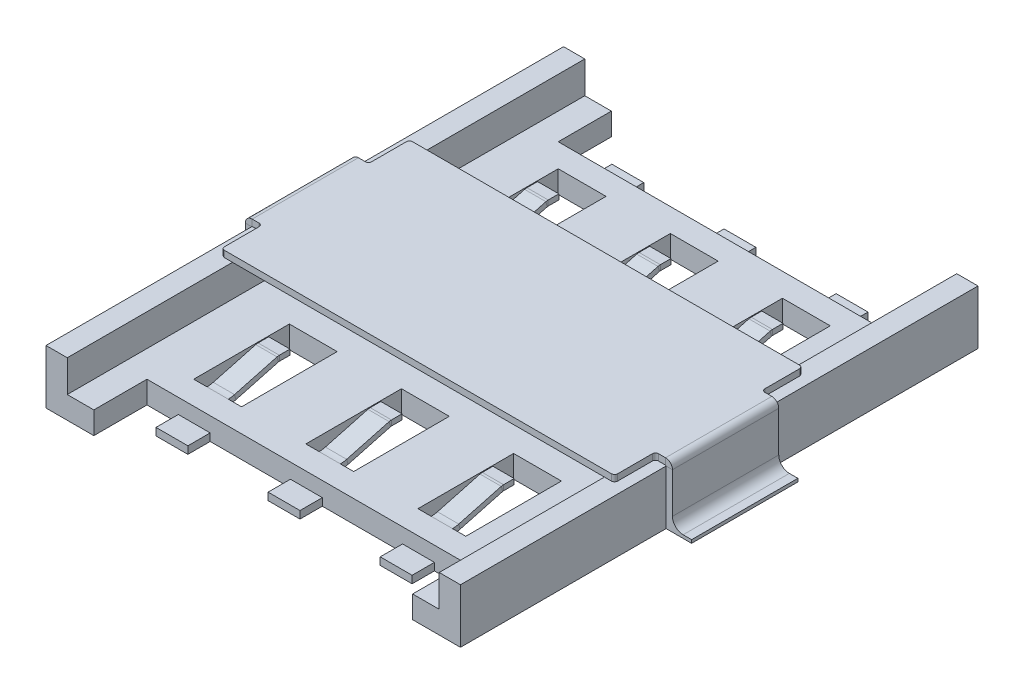
SolidWorks part; units mm, degrees
ref_plane "Front Plane" through (0, 0, 0) normal (0, 0, 1) x (1, 0, 0)
ref_plane "Top Plane" through (0, 0, 0) normal (0, 1, 0) x (1, 0, 0)
ref_plane "Right Plane" through (0, 0, 0) normal (1, 0, 0) x (0, 0, -1)
sketch "Sketch1" plane through (0, 0, 0) normal (0, 1, 0) x (1, 0, 0)
  line L1 (-4.953, 6.1849) -> (4.953, 6.1849)
  line L2 (-4.953, 6.1849) -> (-4.953, -6.1849)
  line L3 (-4.953, -6.1849) -> (4.953, -6.1849)
  line L4 (4.953, 6.1849) -> (4.953, -6.1849)
  point P4 (0, -6.1849)
  point P6 (-4.953, 0)
  dimension "D1" = 9.906
  dimension "D2" = 12.3698
extrude "Boss-Extrude1" add sketch "Sketch1" along normal blind 0.5334
sketch "Sketch2" plane through (0, 0.5334, 0) normal (0, 1, 0) x (1, 0, 0)
  line L0 (-4.953, -6.1849) -> (4.953, -6.1849) construction
  line L1 (-4.953, 6.1849) -> (-4.445, 6.1849)
  line L2 (-4.953, 6.1849) -> (-4.953, -6.1849)
  line L3 (-4.953, -6.1849) -> (-4.445, -6.1849)
  line L4 (-4.445, 6.1849) -> (-4.445, -6.1849)
  line L6 (4.445, -6.1849) -> (4.953, -6.1849)
  line L7 (4.445, -6.1849) -> (4.445, 6.1849)
  line L8 (4.445, 6.1849) -> (4.953, 6.1849)
  line L9 (4.953, -6.1849) -> (4.953, 6.1849)
  dimension "D1" = 0.508
extrude "Boss-Extrude2" add sketch "Sketch2" along normal blind 0.762
sketch "Sketch3" plane through (0, 0.5334, 0) normal (0, 1, 0) x (1, 0, 0)
  line L0 (4.445, 6.1849) -> (-4.445, 6.1849) construction
  line L1 (-3.81, 6.1849) -> (3.81, 6.1849)
  line L2 (-3.81, 6.1849) -> (-3.81, 4.9149)
  line L3 (-3.81, 4.9149) -> (3.81, 4.9149)
  line L4 (3.81, 6.1849) -> (3.81, 4.9149)
  line L5 (-4.445, -6.1849) -> (4.445, -6.1849) construction
  line L6 (-3.81, -6.1849) -> (3.81, -6.1849)
  line L7 (-3.81, -6.1849) -> (-3.81, -4.9149)
  line L8 (-3.81, -4.9149) -> (3.81, -4.9149)
  line L9 (3.81, -6.1849) -> (3.81, -4.9149)
  line L10 (-4.953, 6.1849) -> (-4.953, -6.1849) construction
  point P14 (0, 4.9149)
  point P15 (0, 6.1849)
  point P16 (0, -4.9149)
  dimension "D1" = 1.143
  dimension "D2" = 1.27
extrude "Cut-Extrude1" cut sketch "Sketch3" against normal up to next
sketch "Sketch4" plane through (0, 0.5334, 0) normal (0, 1, 0) x (1, 0, 0)
  line L0 (-3.81, 4.9149) -> (3.81, 4.9149) construction
  line L1 (-3.2512, 4.3561) -> (-2.1082, 4.3561)
  line L2 (-3.2512, 4.3561) -> (-3.2512, 2.0701)
  line L3 (-3.2512, 2.0701) -> (-2.1082, 2.0701)
  line L4 (-2.1082, 4.3561) -> (-2.1082, 2.0701)
  line L5 (-4.953, 6.1849) -> (-4.953, -6.1849) construction
  line L6 (-2.1082, 2.0701) -> (-0.5715, 2.0701) construction
  line L7 (-0.5715, 4.3561) -> (0.5715, 4.3561)
  line L8 (-0.5715, 4.3561) -> (-0.5715, 2.0701)
  line L9 (-0.5715, 2.0701) -> (0.5715, 2.0701)
  line L10 (0.5715, 4.3561) -> (0.5715, 2.0701)
  line L11 (2.1082, 4.3561) -> (3.2512, 4.3561)
  line L12 (2.1082, 4.3561) -> (2.1082, 2.0701)
  line L13 (2.1082, 2.0701) -> (3.2512, 2.0701)
  line L14 (3.2512, 4.3561) -> (3.2512, 2.0701)
  line L15 (0.5715, 2.0701) -> (2.1082, 2.0701) construction
  line L16 (-4.445, 0) -> (4.445, 0) construction
  line L17 (-4.445, -6.1849) -> (-4.445, 6.1849) construction
  line L18 (4.445, 6.1849) -> (4.445, -6.1849) construction
  line L19 (0.5715, -2.0701) -> (2.1082, -2.0701) construction
  line L20 (-2.1082, -2.0701) -> (-0.5715, -2.0701) construction
  line L21 (3.2512, -4.3561) -> (3.2512, -2.0701)
  line L22 (2.1082, -2.0701) -> (3.2512, -2.0701)
  line L23 (2.1082, -4.3561) -> (2.1082, -2.0701)
  line L24 (2.1082, -4.3561) -> (3.2512, -4.3561)
  line L25 (0.5715, -4.3561) -> (0.5715, -2.0701)
  line L26 (-0.5715, -2.0701) -> (0.5715, -2.0701)
  line L27 (-0.5715, -4.3561) -> (-0.5715, -2.0701)
  line L28 (-0.5715, -4.3561) -> (0.5715, -4.3561)
  line L29 (-2.1082, -4.3561) -> (-2.1082, -2.0701)
  line L30 (-3.2512, -2.0701) -> (-2.1082, -2.0701)
  line L31 (-3.2512, -4.3561) -> (-3.2512, -2.0701)
  line L32 (-3.2512, -4.3561) -> (-2.1082, -4.3561)
  point P16 (0, 2.0701)
  dimension "D1" = 0.5588
  dimension "D2" = 2.286
  dimension "D3" = 1.143
  dimension "D4" = 1.7018
extrude "Cut-Extrude2" cut sketch "Sketch4" against normal up to next
sketch "Sketch5" plane through (0, 0, 0) normal (0, -1, 0) x (1, 0, 0)
  line L0 (4.953, 6.1849) -> (4.953, -6.1849) construction
  line L1 (4.953, -1.27) -> (5.1054, -1.27)
  line L2 (4.953, -1.27) -> (4.953, 1.27)
  line L3 (4.953, 1.27) -> (5.1054, 1.27)
  line L4 (5.1054, -1.27) -> (5.1054, 1.27)
  point P6 (4.953, 0)
  dimension "D1" = 2.54
  dimension "D2" = 0.1524
sketch "Sketch6" plane through (0, 0, 0) normal (0, 0, 1) x (1, 0, 0)
  line L0 (4.953, 0) -> (4.953, 1.2954)
  line L1 (4.9403, 1.3081) -> (-4.9403, 1.3081)
  line L2 (-4.953, 0) -> (-4.953, 1.2954)
  arc A0 (4.953, 1.2954) -> (4.9403, 1.3081) centre (4.9403, 1.2954) ccw
  arc A1 (-4.953, 1.2954) -> (-4.9403, 1.3081) centre (-4.9403, 1.2954) cw
  dimension "D1" = 0.0127
sweep "Sweep1" add profiles "Sketch5" path "Sketch6"
sketch "Sketch7" plane through (0, 1.4605, 0) normal (0, 1, 0) x (1, 0, 0)
  line L0 (-4.9403, -1.27) -> (4.9403, -1.27) construction
  line L1 (4.699, -1.27) -> (-4.699, -1.27)
  line L2 (4.699, -1.27) -> (4.699, -2.2479)
  line L3 (4.699, -2.2479) -> (-4.699, -2.2479)
  line L4 (-4.699, -1.27) -> (-4.699, -2.2479)
  line L5 (-4.9403, 1.27) -> (4.9403, 1.27) construction
  line L6 (-4.699, 1.27) -> (4.699, 1.27)
  line L7 (-4.699, 1.27) -> (-4.699, 2.2479)
  line L8 (-4.699, 2.2479) -> (4.699, 2.2479)
  line L9 (4.699, 1.27) -> (4.699, 2.2479)
  line L10 (4.445, -6.1849) -> (4.953, -6.1849) construction
  point P12 (0, -2.2479)
  point P13 (0, 2.2479)
  point P17 (4.699, -6.1849)
  dimension "D1" = 4.4958
extrude "Boss-Extrude3" add sketch "Sketch7" against normal up to surface (0.1524 mm away) up to face at (0, 1.3081, 0)
fillet "Fillet1" radius 0.0762 8 edges at (4.699, 1.3843, 1.27) (4.699, 1.3843, 2.2479) (-4.699, 1.3843, 2.2479) (-4.699, 1.3843, 1.27) (-4.699, 1.3843, -1.27) (-4.699, 1.3843, -2.2479) (4.699, 1.3843, -2.2479) (4.699, 1.3843, -1.27)
sketch "Sketch8" plane through (0, 0, -2.0701) normal (0, 0, -1) x (-1, 0, 0)
  line L0 (0.5715, 0.5334) -> (-0.5715, 0.5334) construction
  line L1 (-0.254, 0.5334) -> (0.254, 0.5334)
  line L2 (-0.254, 0.5334) -> (-0.254, 0.4064)
  line L3 (-0.254, 0.4064) -> (0.254, 0.4064)
  line L4 (0.254, 0.5334) -> (0.254, 0.4064)
  line L5 (3.2512, 0.5334) -> (2.1082, 0.5334) construction
  line L6 (2.4257, 0.5334) -> (2.9337, 0.5334)
  line L7 (2.4257, 0.5334) -> (2.4257, 0.4064)
  line L8 (2.4257, 0.4064) -> (2.9337, 0.4064)
  line L9 (2.9337, 0.5334) -> (2.9337, 0.4064)
  line L10 (-2.1082, 0.5334) -> (-3.2512, 0.5334) construction
  line L11 (-2.9337, 0.5334) -> (-2.4257, 0.5334)
  line L12 (-2.9337, 0.5334) -> (-2.9337, 0.4064)
  line L13 (-2.9337, 0.4064) -> (-2.4257, 0.4064)
  line L14 (-2.4257, 0.5334) -> (-2.4257, 0.4064)
  point P18 (-2.6797, 0.5334)
  point P19 (-2.6797, 0.5334)
  point P20 (0, 0.5334)
  point P21 (0, 0.5334)
  point P22 (2.6797, 0.5334)
  point P23 (2.6797, 0.5334)
  dimension "D1" = 0.508
  dimension "D2" = 0.127
sketch "Sketch9" plane through (0, 0, 0) normal (1, 0, 0) x (0, 0, -1)
  line L0 (2.2199, 0.5531) -> (2.1463, 0.5334) construction
  line L1 (2.1463, 0.5334) -> (2.0701, 0.5334) construction
  line L2 (2.2199, 0.5531) -> (3.2359, 0.8254)
  line L3 (3.2908, 0.8326) -> (3.2629, 0.8326) construction
  line L4 (3.2629, 0.8326) -> (3.2359, 0.8254) construction
  line L5 (3.2359, 0.8254) -> (3.2359, 0.5531) construction
  line L6 (3.2359, 0.5531) -> (2.2199, 0.5531) construction
  line L7 (3.2908, 0.8326) -> (3.5448, 0.8326)
  line L8 (-3.1354, 0.8326) -> (-2.8814, 0.8326)
  line L9 (-4.2063, 0.5531) -> (-3.1903, 0.8254)
  line L10 (-4.3561, 0) -> (-4.3561, 0.5334) construction
  arc A0 (2.0701, 0.5334) -> (2.2199, 0.5531) centre (2.0701, 1.1122) ccw
  arc A1 (3.2359, 0.8254) -> (3.2908, 0.8326) centre (3.2908, 0.6204) cw
  arc A2 (-3.1903, 0.8254) -> (-3.1354, 0.8326) centre (-3.1354, 0.6204) cw
  arc A3 (-4.3561, 0.5334) -> (-4.2063, 0.5531) centre (-4.3561, 1.1122) ccw
  dimension "D1" = 165
  dimension "D2" = 0.0762
  dimension "D3" = 1.016
  dimension "D4" = 0.254
  dimension "D5" = 0.0279
  dimension "D6" = 2
sweep "Sweep2" add profiles "Sketch8" path "Sketch9"
sketch "Sketch10" plane through (0, 0, 4.3561) normal (0, 0, -1) x (-1, 0, 0)
  line L0 (0.5715, 0.5334) -> (-0.5715, 0.5334) construction
  line L1 (-0.254, 0.5334) -> (0.254, 0.5334)
  line L2 (-0.254, 0.5334) -> (-0.254, 0.4064)
  line L3 (-0.254, 0.4064) -> (0.254, 0.4064)
  line L4 (0.254, 0.5334) -> (0.254, 0.4064)
  line L5 (-2.1082, 0.5334) -> (-3.2512, 0.5334) construction
  line L6 (-2.9337, 0.5334) -> (-2.4257, 0.5334)
  line L7 (-2.9337, 0.5334) -> (-2.9337, 0.4064)
  line L8 (-2.9337, 0.4064) -> (-2.4257, 0.4064)
  line L9 (-2.4257, 0.5334) -> (-2.4257, 0.4064)
  line L10 (3.2512, 0.5334) -> (2.1082, 0.5334) construction
  line L11 (2.4257, 0.5334) -> (2.9337, 0.5334)
  line L12 (2.4257, 0.5334) -> (2.4257, 0.4064)
  line L13 (2.4257, 0.4064) -> (2.9337, 0.4064)
  line L14 (2.9337, 0.5334) -> (2.9337, 0.4064)
  line L15 (2.4257, 0.5334) -> (2.9337, 0.5334) construction
  line L16 (0.254, 0.5334) -> (0.254, 0.4064) construction
  point P6 (0, 0.5334)
  point P20 (2.6797, 0.5334)
  point P21 (2.6797, 0.5334)
  point P22 (-2.6797, 0.5334)
  point P23 (-2.6797, 0.5334)
sweep "Sweep3" add profiles "Sketch10" path "Sketch9<3>"
sketch "Sketch9<3>" plane through (0, 0, 0) normal (1, 0, 0) x (0, 0, -1) same geometry as "Sketch9"
sketch "Sketch11" plane through (0, 0, 0) normal (0, -1, 0) x (1, 0, 0)
  line L0 (3.81, -4.9149) -> (-3.81, -4.9149) construction
  line L1 (-3.0607, -4.9149) -> (-2.2987, -4.9149)
  line L2 (-3.0607, -4.9149) -> (-3.0607, -5.4483)
  line L3 (-3.0607, -5.4483) -> (-2.2987, -5.4483)
  line L4 (-2.2987, -4.9149) -> (-2.2987, -5.4483)
  line L5 (-2.2987, -5.4483) -> (-0.381, -5.4483) construction
  line L6 (-0.381, -4.9149) -> (0.381, -4.9149)
  line L7 (-0.381, -4.9149) -> (-0.381, -5.4483)
  line L8 (-0.381, -5.4483) -> (0.381, -5.4483)
  line L9 (0.381, -4.9149) -> (0.381, -5.4483)
  line L10 (2.2987, -4.9149) -> (3.0607, -4.9149)
  line L11 (2.2987, -4.9149) -> (2.2987, -5.4483)
  line L12 (2.2987, -5.4483) -> (3.0607, -5.4483)
  line L13 (3.0607, -4.9149) -> (3.0607, -5.4483)
  line L14 (0.381, -5.4483) -> (2.2987, -5.4483) construction
  line L15 (-0.5715, -4.3561) -> (0.5715, -4.3561) construction
  line L16 (2.1082, -4.3561) -> (3.2512, -4.3561) construction
  point P14 (0, -4.9149)
  point P17 (0, -4.3561)
  point P18 (2.6797, -4.9149)
  point P21 (2.6797, -4.3561)
  dimension "D1" = 0.762
  dimension "D2" = 0.5334
extrude "Boss-Extrude4" add sketch "Sketch11" against normal blind 0.1778
mirror "Mirror1" about plane through (0, 0, 0) normal (0, 0, 1) of "Boss-Extrude4"
sketch "Sketch12" plane through (0, 0, 0) normal (0, -1, 0) x (1, 0, 0)
  line L1 (5.1054, -1.27) -> (5.5626, -1.27)
  line L2 (5.1054, -1.27) -> (5.1054, 1.27)
  line L3 (5.1054, 1.27) -> (5.5626, 1.27)
  line L4 (5.5626, -1.27) -> (5.5626, 1.27)
  dimension "D1" = 0.4572
extrude "Boss-Extrude5" add sketch "Sketch12" against normal blind 0.0762
mirror "Mirror4" about plane through (0, 0, 0) normal (1, 0, 0) of "Boss-Extrude5"
fillet "Fillet2" radius 0.254 2 edges at (5.1054, 0.0762, 0) (-5.1054, 0.0762, 0)
